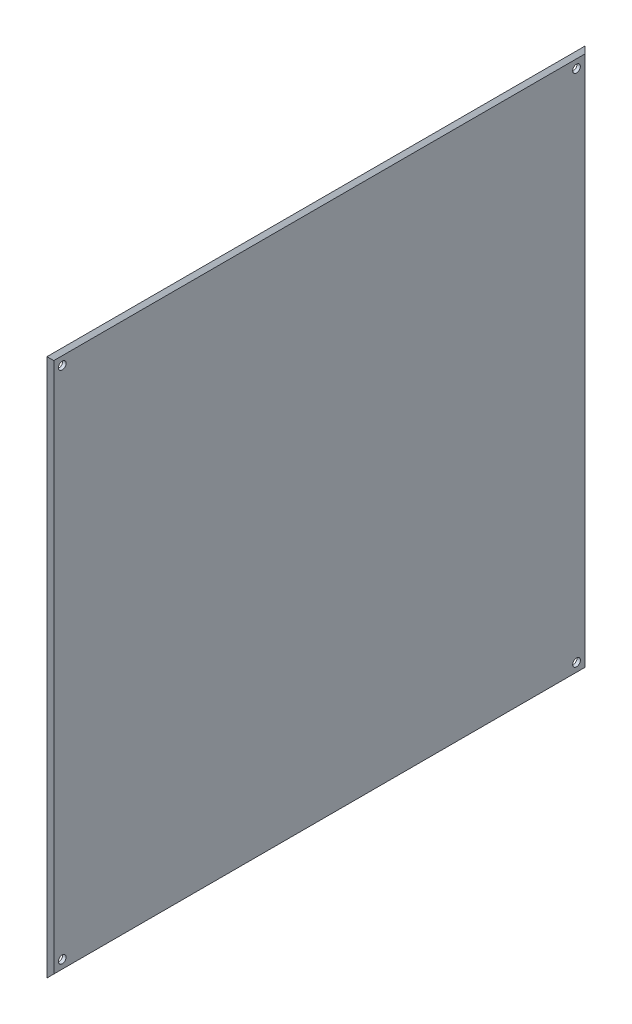
SolidWorks part; units mm, degrees
material "Brass"
ref_plane "Front Plane" through (0, 0, 0) normal (0, 0, 1) x (1, 0, 0)
ref_plane "Top Plane" through (0, 0, 0) normal (0, 1, 0) x (1, 0, 0)
ref_plane "Right Plane" through (0, 0, 0) normal (1, 0, 0) x (0, 0, -1)
sketch "Sketch1" plane through (0, 0, 0) normal (1, 0, 0) x (0, 0, -1)
  line L1 (0, 0) -> (316, 0)
  line L2 (0, 0) -> (0, 316)
  line L3 (0, 316) -> (316, 316)
  line L4 (316, 0) -> (316, 316)
  dimension "D1" = 316
  dimension "D2" = 316
extrude "Boss-Extrude1" add sketch "Sketch1" along normal blind 2 contours L2 L3 L4 L1
chamfer "Chamfer1" distance 2 4 edges at (2, 158, 0) (2, 316, -158) (2, 158, -316) (2, 0, -158)
sketch "Sketch4" plane through (2, 0, 0) normal (1, 0, 0) x (0, 0, -1)
  line L0 (7, 309) -> (309, 309) construction
  line L1 (309, 309) -> (309, 7) construction
  line L2 (309, 7) -> (7, 7) construction
  line L3 (7, 7) -> (7, 309) construction
  line L4 (2, 2) -> (314, 2) construction
  line L5 (2, 314) -> (2, 2) construction
  point P0 (7, 309)
  point P1 (309, 309)
  point P12 (309, 309)
  point P14 (309, 7)
  point P16 (7, 7)
  point P18 (7, 309)
  dimension "D1" = 302
  dimension "D2" = 5
  dimension "D3" = 5
  dimension "D4" = 302
  dimension "D5" = 0
  dimension "D6" = 0
  dimension "D7" = 0
  dimension "D8" = 0
hole_wizard "M4 Clearance Hole1" positions "Sketch4" profile "Sketch5" hole size "M4" standard "ANSI Metric"
sketch "Sketch5" plane through (2, 309, -7) normal (0, 1, 0) x (0, 0, -1)
  line L0 (0, 0) -> (0, 31.3519)
  line L1 (0, 31.3519) -> (2.25, 30)
  line L2 (2.25, 30) -> (2.25, 0)
  line L5 (2.25, 0) -> (0, 0)
  line L10 (0, 31.3519) -> (-2.25, 30) construction
  line L11 (0, -6.35) -> (0, 107.95) construction
  dimension "Hole Dia." = 4.5
  dimension "Hole Depth" = 30
  dimension "Drill Angle" = 118
